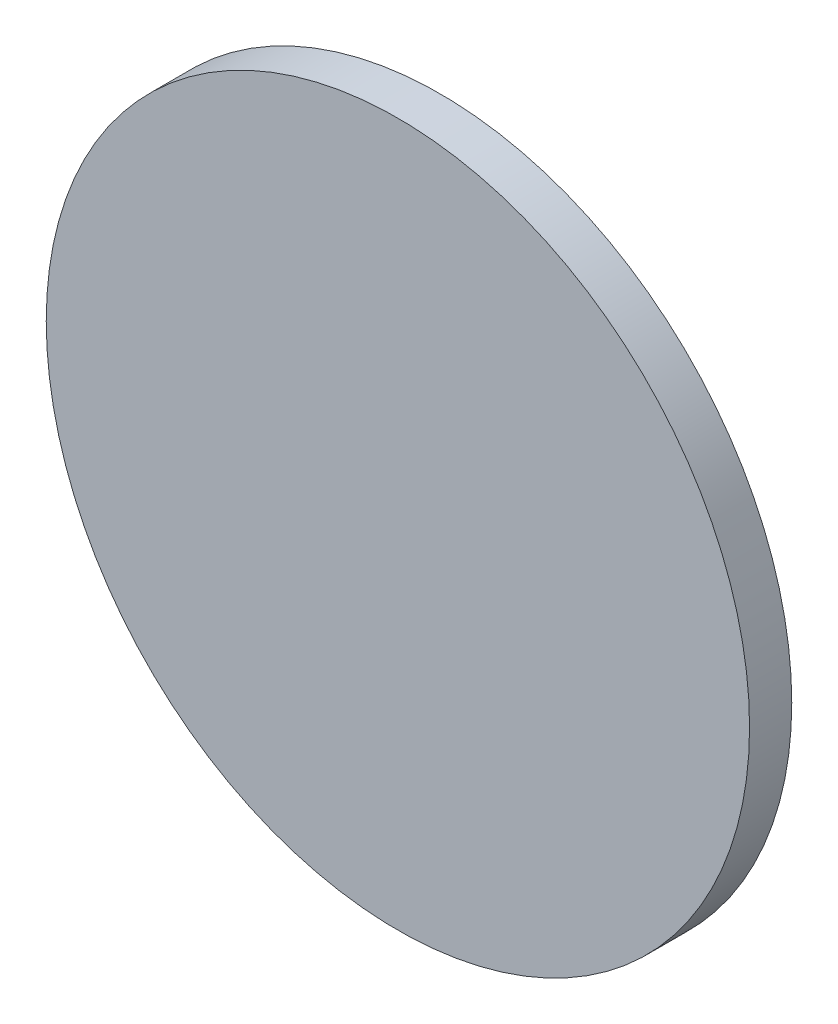
SolidWorks part; units mm, degrees
ref_plane "前视基准面" through (0, 0, 0) normal (0, 0, 1) x (1, 0, 0)
ref_plane "上视基准面" through (0, 0, 0) normal (0, 1, 0) x (1, 0, 0)
ref_plane "右视基准面" through (0, 0, 0) normal (1, 0, 0) x (0, 0, -1)
other "Configuration Table"
sketch "Sketch1" plane through (0, 0, 0) normal (0, 0, 1) x (1, 0, 0)
  circle A0 centre (0, 0) radius 125
extrude "Boss-Extrude1" add sketch "Sketch1" along normal blind 15
ref_plane "base_bottom_face" through (0, 0, 0) normal (0, 0, 1) x (1, 0, 0)
ref_plane "base_top_face" through (0, 0, 15) normal (0, 0, 1) x (1, 0, 0)
sketch3d "3DSketch1"
  line L0 (0, 0, 0) -> (0, 0, 15) construction
ref_axis "base_center_axis" through (0, 0, 0) along (0, 0, 1)
